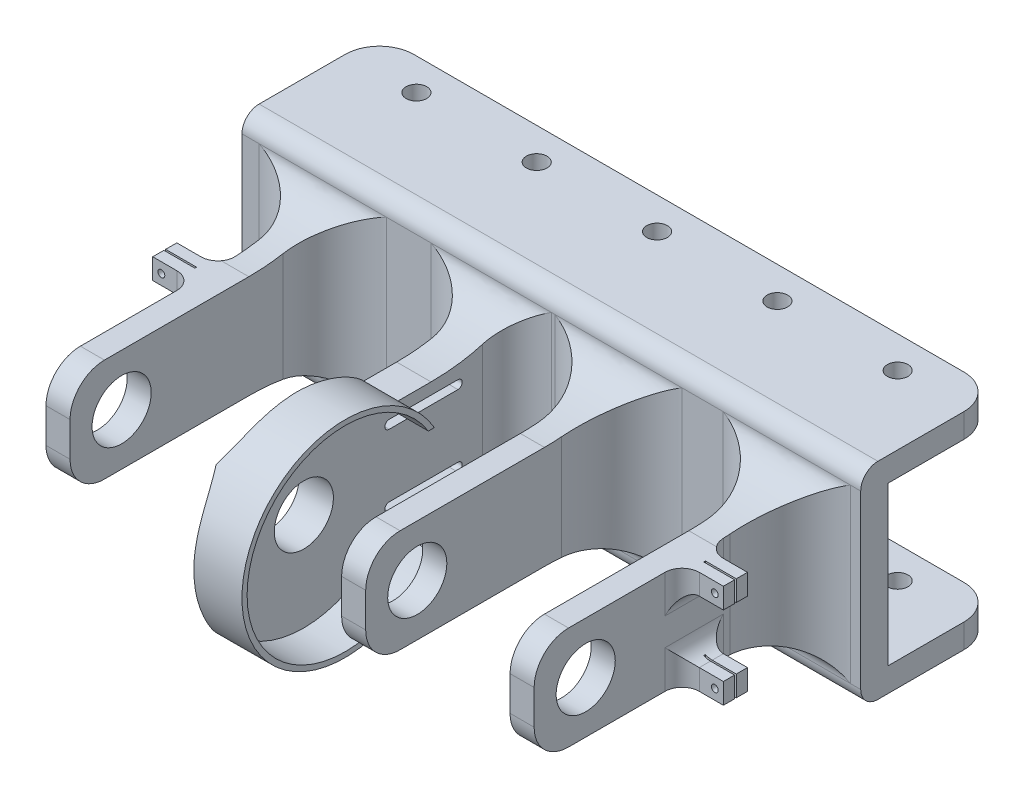
SolidWorks part; units mm, degrees
ref_plane "前视基准面" through (0, 0, 0) normal (0, 0, 1) x (1, 0, 0)
ref_plane "上视基准面" through (0, 0, 0) normal (0, 1, 0) x (1, 0, 0)
ref_plane "右视基准面" through (0, 0, 0) normal (1, 0, 0) x (0, 0, -1)
other "Configuration Table"
sketch "草图1" plane through (0, 0, 0) normal (1, 0, 0) x (0, 0, -1)
  line L1 (0, 0) -> (40, 0)
  line L2 (0, 0) -> (0, 60)
  line L3 (0, 60) -> (40, 60)
  line L4 (40, 0) -> (40, 60)
  dimension "D1" = 60
  dimension "D2" = 40
extrude "凸台-拉伸1" add sketch "草图1" along normal blind 45 and the other way blind 135
sketch "草图2" plane through (45, 0, 0) normal (1, 0, 0) x (0, 0, -1)
  line L0 (40, 0) -> (40, 60) construction
  line L1 (40, 53) -> (8, 53)
  line L2 (40, 53) -> (40, 7)
  line L3 (40, 7) -> (8, 7)
  line L4 (8, 53) -> (8, 7)
  line L5 (0, 0) -> (40, 0) construction
  line L6 (40, 60) -> (0, 60) construction
  line L7 (0, 60) -> (0, 0) construction
  dimension "D1" = 7
  dimension "D2" = 7
  dimension "D3" = 8
extrude "切除-拉伸1" cut sketch "草图2" against normal up to next
sketch "草图3" plane through (0, 0, 0) normal (0, -1, 0) x (-1, 0, 0)
  line L0 (135, 30.75) -> (-45, 30.75) construction
  line L1 (135, 0) -> (135, 40) construction
  line L2 (-45, 0) -> (-45, 40) construction
  line L5 (-45, 0) -> (135, 0) construction
  circle A2 centre (45, 30.75) radius 3
  circle A4 centre (10, 30.75) radius 3
  circle A6 centre (-25, 30.75) radius 3
  circle A7 centre (115, 30.75) radius 3
  circle A8 centre (80, 30.75) radius 3
  dimension "D5" = 6
  dimension "D6" = 35
  dimension "D7" = 35
  dimension "D10" = 35
  dimension "D11" = 6
  dimension "D13" = 6
  dimension "D9" = 6
  dimension "D8" = 6
  dimension "D4" = 20
  dimension "D12" = 30.75
  dimension "D14" = 35
extrude "切除-拉伸2" cut sketch "草图3" against normal blind 87
sketch "草图4" plane through (0, 0, 0) normal (0, 0, 1) x (1, 0, 0)
  line L1 (-65, 45) -> (-55, 45)
  line L2 (-65, 45) -> (-65, 15)
  line L3 (-65, 15) -> (-55, 15)
  line L4 (-55, 45) -> (-55, 15)
  line L6 (-135, 60) -> (-135, 0) construction
  line L7 (45, 0) -> (-135, 0) construction
  line L9 (-29, 45) -> (-22, 45)
  line L10 (-29, 45) -> (-29, 15)
  line L11 (-29, 15) -> (-22, 15)
  line L12 (-22, 45) -> (-22, 15)
  line L13 (20, 45) -> (27, 45)
  line L14 (20, 45) -> (20, 15)
  line L15 (20, 15) -> (27, 15)
  line L16 (27, 45) -> (27, 15)
  line L19 (-115, 45) -> (-108, 45)
  line L20 (-115, 45) -> (-115, 15)
  line L21 (-115, 15) -> (-108, 15)
  line L22 (-108, 45) -> (-108, 15)
  dimension "D1" = 70
  dimension "D2" = 10
  dimension "D3" = 43
  dimension "D4" = 15
  dimension "D5" = 26
  dimension "D6" = 7
  dimension "D7" = 42
  dimension "D8" = 7
  dimension "D9" = 7
extrude "凸台-拉伸2" add sketch "草图4" along normal blind 77
sketch "草图5" plane through (-55, 0, 0) normal (1, 0, 0) x (0, 0, -1)
  line L0 (-77, 30) -> (-36.3516, 30) construction
  line L1 (-77, 15) -> (-77, 45) construction
  line L2 (0, 15) -> (0, 45) construction
  circle A0 centre (-62, 30) radius 30
  dimension "D2" = 60
  dimension "D1" = 62
extrude "凸台-拉伸3" add sketch "草图5" along normal blind 12 and the other way blind 2
sketch "草图7" plane through (-43, 0, 0) normal (1, 0, 0) x (0, 0, -1)
  circle A0 centre (-62, 30) radius 28.5
  dimension "D1" = 57
extrude "切除-拉伸4" cut sketch "草图7" against normal blind 12
sketch "草图8" plane through (-43, 0, 0) normal (1, 0, 0) x (0, 0, -1)
  line L0 (-36.0192, 45) -> (0, 45) construction
  line L1 (-29.5126, 45) -> (-41.5126, 45)
  line L2 (-29.5126, 45) -> (-29.5126, 15)
  line L3 (-29.5126, 15) -> (-41.5126, 15)
  line L4 (-41.5126, 45) -> (-41.5126, 15)
  dimension "D1" = 30
  dimension "D2" = 12
extrude "切除-拉伸5" cut sketch "草图8" against normal blind 12
sketch "草图9" plane through (-55, 0, 0) normal (1, 0, 0) x (0, 0, -1)
  line L0 (0, 30) -> (-72.8107, 30) construction
  line L1 (0, 60) -> (0, 0) construction
  line L2 (-37.1752, 40.4) -> (-17.1752, 40.4) construction
  line L3 (-37.1752, 41.65) -> (-17.1752, 41.65)
  line L4 (-37.1752, 39.15) -> (-17.1752, 39.15)
  line L5 (-37.1752, 19.6) -> (-17.1752, 19.6) construction
  line L6 (-37.1752, 20.85) -> (-17.1752, 20.85)
  line L7 (-37.1752, 18.35) -> (-17.1752, 18.35)
  line L8 (-36.0192, 15) -> (0, 15) construction
  circle A0 centre (-62, 30) radius 8.6
  arc A1 (-37.1752, 41.65) -> (-37.1752, 39.15) centre (-37.1752, 40.4) ccw
  arc A2 (-17.1752, 39.15) -> (-17.1752, 41.65) centre (-17.1752, 40.4) ccw
  arc A3 (-37.1752, 20.85) -> (-37.1752, 18.35) centre (-37.1752, 19.6) ccw
  arc A4 (-17.1752, 18.35) -> (-17.1752, 20.85) centre (-17.1752, 19.6) ccw
  point P8 (-27.1752, 40.4)
  point P13 (-27.1752, 19.6)
  dimension "D2" = 17.2
  dimension "D1" = 62
  dimension "D3" = 20
  dimension "D4" = 20
  dimension "D5" = 2.5
  dimension "D6" = 2.5
  dimension "D7" = 20.8
  dimension "D8" = 4.6
extrude "切除-拉伸6" cut sketch "草图9" against normal up to next
sketch "草图10" plane through (-22, 0, 0) normal (1, 0, 0) x (0, 0, -1)
  line L0 (0, 30) -> (-77, 30) construction
  line L1 (0, 60) -> (0, 0) construction
  line L2 (-77, 15) -> (-77, 45) construction
  line L3 (0, 15) -> (0, 45) construction
  circle A0 centre (-62, 30) radius 8.6
  dimension "D2" = 17.2
  dimension "D1" = 62
extrude "切除-拉伸7" cut sketch "草图10" against normal up to next
sketch "草图11" plane through (27, 0, 0) normal (1, 0, 0) x (0, 0, -1)
  line L0 (-77, 30) -> (-40.7787, 30) construction
  line L1 (-77, 15) -> (-77, 45) construction
  line L2 (0, 15) -> (0, 45) construction
  circle A0 centre (-62, 30) radius 8.6
  dimension "D2" = 17.2
  dimension "D1" = 62
extrude "切除-拉伸8" cut sketch "草图11" against normal up to next
sketch "草图12" plane through (27, 0, 0) normal (1, 0, 0) x (0, 0, -1)
  line L0 (-77, 45) -> (0, 45) construction
  line L2 (-33.95, 45) -> (-26.95, 45)
  line L3 (-33.95, 45) -> (-33.95, 39)
  line L4 (-33.95, 39) -> (-26.95, 39)
  line L5 (-26.95, 45) -> (-26.95, 39)
  line L10 (-77, 15) -> (-77, 45) construction
  line L11 (-77, 15) -> (0, 15) construction
  line L12 (-33.95, 15) -> (-26.95, 15)
  line L13 (-33.95, 15) -> (-33.95, 21)
  line L14 (-33.95, 21) -> (-26.95, 21)
  line L15 (-26.95, 15) -> (-26.95, 21)
  dimension "D1" = 43.05
  dimension "D2" = 7
  dimension "D3" = 6
  dimension "D4" = 7
  dimension "D5" = 6
extrude "凸台-拉伸4" add sketch "草图12" along normal blind 12
sketch "草图13" plane through (0, 15, 0) normal (0, -1, 0) x (-1, 0, 0)
  line L0 (-39, -30.45) -> (-115.4089, -30.45) construction
  line L1 (-39, -33.95) -> (-39, -26.95) construction
  line L3 (-39, -30.7) -> (-30, -30.7)
  line L4 (-39, -30.7) -> (-39, -30.2)
  line L5 (-39, -30.2) -> (-30, -30.2)
  line L6 (-30, -30.7) -> (-30, -30.2)
  line L7 (-27, -26.95) -> (-27, 0) construction
  dimension "D1" = 3
  dimension "D2" = 0.5
  dimension "D3" = 0.25
extrude "切除-拉伸9" cut sketch "草图13" against normal blind 40
fillet "圆角3" radius 10 8 edges at (23.5, 15, 0) (-25.5, 15, 0) (-60, 15, 0) (-60, 45, 0) (-25.5, 45, 0) (23.5, 45, 0) (-111.5, 45, 0) (-111.5, 15, 0) second distance 25 first distance on face at (-45, 30, 0)
fillet "圆角4" radius 15 4 edges second distance 20 first distance on face at (-45, 30, 0)
fillet "圆角6" radius 10 6 edges at (-25.5, 15, 77) (-25.5, 45, 77) (23.5, 15, 77) (23.5, 45, 77) (-111.5, 45, 77) (-111.5, 15, 77)
fillet "圆角18" radius 18 3 edges at (-57, 45, 56.5096) (-57, 30, 77) (-57, 15, 56.5096)
ref_plane "基准面1" through (-60, 0, 0) normal (-1, 0, 0) x (0, 0, 1)
sketch "草图16" plane through (-115, 0, 0) normal (-1, 0, 0) x (0, 0, 1)
  line L0 (77, 30) -> (27.4435, 30) construction
  line L1 (77, 35) -> (77, 25) construction
  line L2 (67, 45) -> (25, 45) construction
  line L3 (26.95, 45) -> (33.95, 45)
  line L4 (26.95, 45) -> (26.95, 39)
  line L5 (26.95, 39) -> (33.95, 39)
  line L6 (33.95, 45) -> (33.95, 39)
  line L7 (67, 15) -> (25, 15) construction
  line L8 (26.95, 15) -> (33.95, 15)
  line L9 (26.95, 15) -> (26.95, 21)
  line L10 (26.95, 21) -> (33.95, 21)
  line L11 (33.95, 15) -> (33.95, 21)
  line L12 (77, 45) -> (77, 15) construction
  dimension "D1" = 43.05
  dimension "D2" = 7
  dimension "D3" = 6
  dimension "D4" = 7
  dimension "D5" = 6
extrude "凸台-拉伸5" add sketch "草图16" along normal blind 12
sketch "草图17" plane through (0, 15, 0) normal (0, -1, 0) x (-1, 0, 0)
  line L0 (127, -30.45) -> (122.6407, -30.45) construction
  line L1 (127, -26.95) -> (127, -33.95) construction
  line L2 (115, -67) -> (115, -33.95) construction
  line L3 (127, -30.7) -> (118, -30.7)
  line L4 (127, -30.7) -> (127, -30.2)
  line L5 (127, -30.2) -> (118, -30.2)
  line L6 (118, -30.7) -> (118, -30.2)
  dimension "D1" = 0.5
  dimension "D2" = 0.25
  dimension "D3" = 3
extrude "切除-拉伸12" cut sketch "草图17" against normal blind 36
sketch "草图18" plane through (-115, 0, 0) normal (-1, 0, 0) x (0, 0, 1)
  line L0 (77, 30) -> (33.9049, 30) construction
  line L1 (77, 35) -> (77, 25) construction
  line L2 (0, 60) -> (0, 0) construction
  circle A0 centre (62, 30) radius 8.6
  dimension "D2" = 17.2
  dimension "D1" = 62
extrude "切除-拉伸13" cut sketch "草图18" against normal up to next
fillet "圆角17" radius 5 12 edges at (27, 21, 30.45) (27, 18, 26.95) (27, 42, 26.95) (27, 39, 30.45) (27, 42, 33.95) (27, 18, 33.95) (-115, 18, 26.95) (-115, 42, 26.95) (-115, 21, 30.45) (-115, 18, 33.95) (-115, 39, 30.45) (-115, 42, 33.95)
sketch "草图14" plane through (0, 0, 33.95) normal (0, 0, 1) x (1, 0, 0)
  line L0 (39, 18) -> (120.2445, 18) construction
  line L1 (39, 21) -> (39, 15) construction
  line L2 (39, 42) -> (120.2445, 42) construction
  line L3 (39, 45) -> (39, 39) construction
  line L4 (-127, 42) -> (-59.3016, 42) construction
  line L5 (-127, 39) -> (-127, 45) construction
  line L6 (-127, 18) -> (-59.3016, 18) construction
  line L7 (-127, 15) -> (-127, 21) construction
  circle A0 centre (36.5, 42) radius 1
  circle A1 centre (36.5, 18) radius 1
  circle A2 centre (-124.5, 42) radius 1
  circle A3 centre (-124.5, 18) radius 1
  dimension "D2" = 2
  dimension "D3" = 2
  dimension "D5" = 2
  dimension "D6" = 2
  dimension "D1" = 2.5
  dimension "D4" = 2.5
  dimension "D7" = 2.5
  dimension "D8" = 2.5
extrude "切除-拉伸10" cut sketch "草图14" against normal blind 10
fillet "圆角19" radius 10 1 edges
fillet "圆角20" radius 15 3 edges first distance on face at (-45, 30, 0)
fillet "圆角21" radius 10 4 edges at (-135, 3.5, -40) (-135, 56.5, -40) (45, 56.5, -40) (45, 3.5, -40)
fillet "圆角22" radius 5 2 edges at (-45, 60, 0) (-45, 0, 0)
